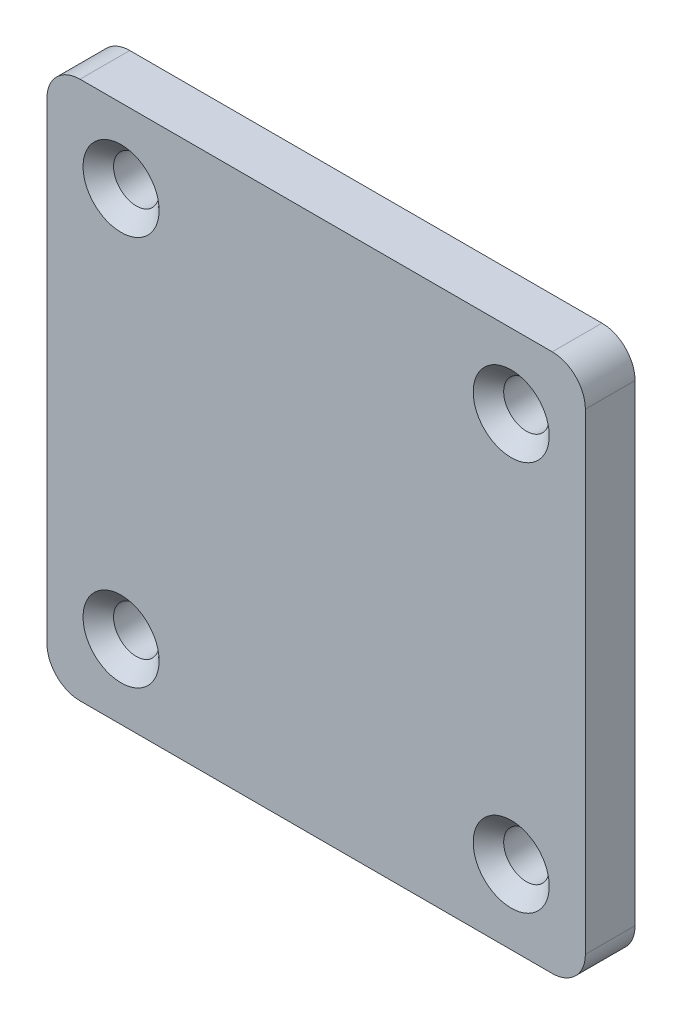
SolidWorks part; units mm, degrees
material "ABS"
ref_plane "Front Plane" through (0, 0, 0) normal (0, 0, 1) x (1, 0, 0)
ref_plane "Top Plane" through (0, 0, 0) normal (0, 1, 0) x (1, 0, 0)
ref_plane "Right Plane" through (0, 0, 0) normal (1, 0, 0) x (0, 0, -1)
sketch "Sketch1" plane through (0, 0, 0) normal (0, 0, 1) x (1, 0, 0)
  line L1 (32.5, -32.5) -> (-32.5, -32.5)
  line L2 (32.5, -32.5) -> (32.5, 32.5)
  line L3 (32.5, 32.5) -> (-32.5, 32.5)
  line L4 (-32.5, -32.5) -> (-32.5, 32.5)
  line L5 (32.5, -32.5) -> (-32.5, 32.5) construction
  line L6 (32.5, 32.5) -> (-32.5, -32.5) construction
  point P0 (0, 0)
  dimension "D1" = 65
  dimension "D2" = 65
extrude "Boss-Extrude1" add sketch "Sketch1" along normal blind 6
sketch "Sketch4" plane through (0, 0, 6) normal (0, 0, 1) x (1, 0, 0)
  line L0 (-23.5502, 23.5502) -> (0, 0) construction
  line L1 (0, 0) -> (0, 33.305) construction
  circle A0 centre (0, 0) radius 33.305 construction
  circle A1 centre (-23.5502, 23.5502) radius 2.75
  circle A2 centre (23.5502, 23.5502) radius 2.75
  circle A3 centre (23.5502, -23.5502) radius 2.75
  circle A4 centre (-23.5502, -23.5502) radius 2.75
  point P15 (0, 0)
  dimension "D1" = 66.61
  dimension "D2" = 5.5
  dimension "D3" = 45
  dimension "D4" = 4
extrude "Cut-Extrude1" cut sketch "Sketch4" against normal up to next
sketch "Sketch9" plane through (0, 0, 6) normal (0, 0, 1) x (1, 0, 0)
  line L1 (-32.5, 32.5) -> (32.5, 32.5)
  line L2 (-32.5, 32.5) -> (-32.5, -32.5)
  line L3 (-32.5, -32.5) -> (32.5, -32.5)
  line L4 (32.5, 32.5) -> (32.5, -32.5)
  circle M17 centre (-23.5502, -23.5502) radius 2.75
  circle M18 centre (23.5502, -23.5502) radius 2.75
  circle M19 centre (23.5502, 23.5502) radius 2.75
  circle M20 centre (-23.5502, 23.5502) radius 2.75
  line M21 (-32.5, 32.5) -> (-32.5, -32.5)
  line M22 (-32.5, -32.5) -> (32.5, -32.5)
  line M23 (32.5, -32.5) -> (32.5, 32.5)
  line M24 (32.5, 32.5) -> (-32.5, 32.5)
extrude "Boss-Extrude2" add sketch "Sketch9" against normal blind 4 contours M24 M21 M22 M23 M18 M20 M19 M17 region at (0, 0, 6)
hole_wizard "CSK for M4 Hex Socket Countersunk Head Screw1" positions "Sketch10" profile "Sketch12" countersink size "M4" standard "DIN" end condition up to next
sketch "Sketch10" plane through (0, 0, 6) normal (0, 0, -1) x (-1, 0, 0)
  point P0 (23.5502, 23.5502)
  point P3 (-23.5502, 23.5502)
  point P6 (23.5502, -23.5502)
  point P9 (-23.5502, -23.5502)
sketch "Sketch12" plane through (-23.5502, 23.5502, 6) normal (1, 0, 0) x (0, -1, 0)
  line L0 (0, 0) -> (0, 6)
  line L1 (0, 6) -> (2.25, 6)
  line L2 (2.25, 6) -> (2.25, 2.34)
  line L3 (2.25, 2.34) -> (4.59, 0)
  line L5 (4.59, 0) -> (0, 0)
  line L6 (-2.25, 2.34) -> (-4.59, 0) construction
  line L11 (0, -6.35) -> (0, 107.95) construction
  dimension "Thru Hole Dia." = 4.5
  dimension "Thru Hole Depth" = 6
  dimension "Near C'Sink Dia." = 9.18
  dimension "Near C'Sink Angle" = 90
sketch "Sketch5" plane through (0, 0, 6) normal (0, 0, 1) x (1, 0, 0)
  line L0 (-18.3002, -23.5502) -> (-12.5, -30)
  line L5 (-12.5, -30) -> (0, -30)
  line L6 (-23.5502, -23.5502) -> (0, 0) construction
  line L7 (-32.5, -32.5) -> (32.5, -32.5) construction
  line L8 (-23.5502, -23.5502) -> (-18.3002, -23.5502) construction
  line L9 (-23.5502, -23.5502) -> (-23.5502, -18.3002) construction
  line L10 (-30, -12.5) -> (-30, 0)
  line L11 (-23.5502, -18.3002) -> (-30, -12.5)
  line L12 (-12.5, 30) -> (0, 30)
  line L13 (-18.3002, 23.5502) -> (-12.5, 30)
  line L14 (-23.5502, 18.3002) -> (-30, 12.5)
  line L15 (-30, 12.5) -> (-30, 0)
  line L16 (30, 12.5) -> (30, 0)
  line L17 (23.5502, 18.3002) -> (30, 12.5)
  line L18 (18.3002, 23.5502) -> (12.5, 30)
  line L19 (12.5, 30) -> (0, 30)
  line L20 (12.5, -30) -> (0, -30)
  line L21 (18.3002, -23.5502) -> (12.5, -30)
  line L22 (23.5502, -18.3002) -> (30, -12.5)
  line L23 (30, -12.5) -> (30, 0)
  arc A0 (-23.5502, -18.3002) -> (-18.3002, -23.5502) centre (-23.5502, -23.5502) cw
  circle A1 centre (-23.5502, -23.5502) radius 2.75 construction
  arc A2 (-18.3002, 23.5502) -> (-23.5502, 18.3002) centre (-23.5502, 23.5502) cw
  arc A3 (23.5502, 18.3002) -> (18.3002, 23.5502) centre (23.5502, 23.5502) cw
  arc A4 (18.3002, -23.5502) -> (23.5502, -18.3002) centre (23.5502, -23.5502) cw
  point P0 (-23.5502, -23.5502)
  point P42 (0, 0)
  dimension "D2" = 2.5
  dimension "D1" = 2.5
  dimension "D4" = 25
  dimension "D3" = 4
extrude "Cut-Extrude2" cut sketch "Sketch5" along normal blind 5 from surface starting at face at (-20.8002, -23.5502, 0)
fillet "Fillet1" radius 4 4 edges at (-32.5, 32.5, 3) (32.5, 32.5, 3) (32.5, -32.5, 3) (-32.5, -32.5, 3)
